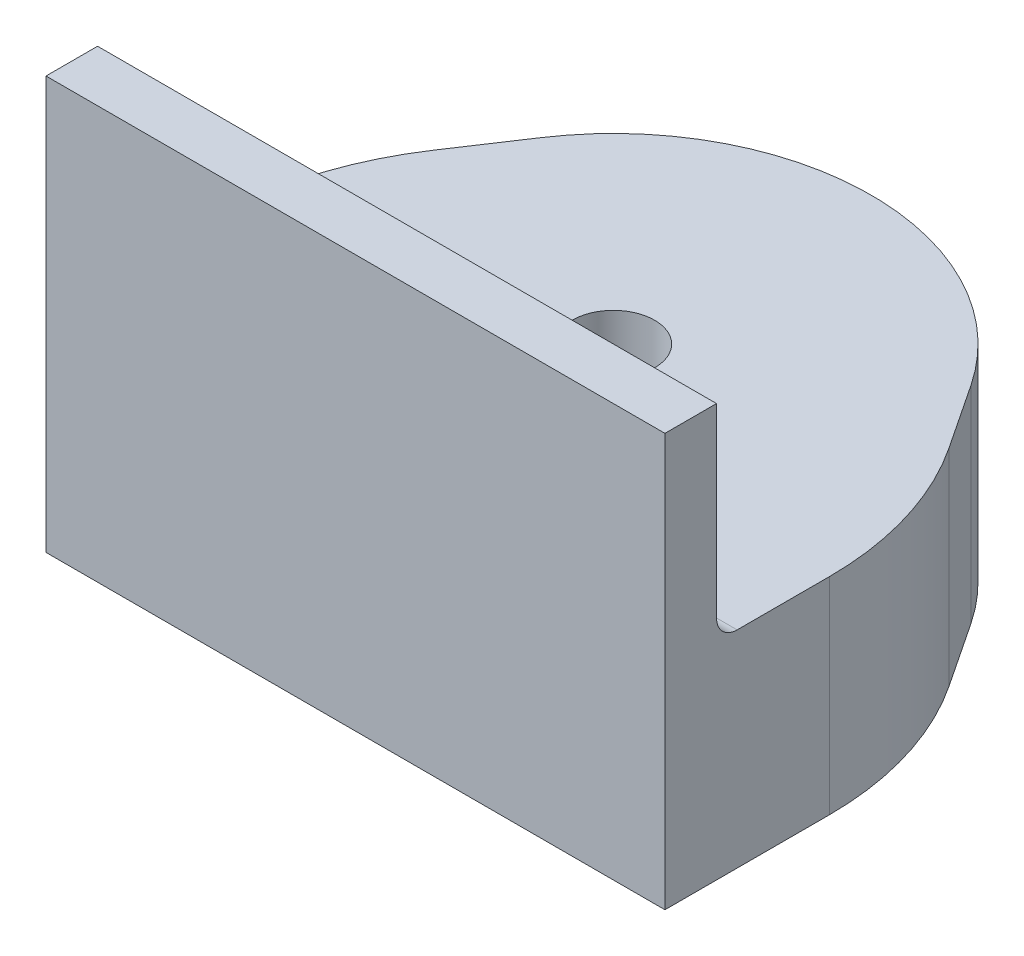
SolidWorks part; units mm, degrees
ref_plane "Front Plane" through (0, 0, 0) normal (0, 0, 1) x (1, 0, 0)
ref_plane "Top Plane" through (0, 0, 0) normal (0, 1, 0) x (1, 0, 0)
ref_plane "Right Plane" through (0, 0, 0) normal (1, 0, 0) x (0, 0, -1)
sketch "Sketch1" plane through (0, 0, 0) normal (0, 1, 0) x (1, 0, 0)
  line L0 (30, -25) -> (-30, -25)
  line L5 (-30, -25) -> (-30, 0)
  line L6 (-30, 0) -> (-20.8333, 13.8193)
  line L7 (0, 0) -> (0, -25) construction
  line L8 (30, -25) -> (30, 0)
  line L9 (30, 0) -> (20.8333, 13.8193)
  circle A0 centre (0, 0) radius 4
  arc A1 (20.8333, 13.8193) -> (-20.8333, 13.8193) centre (0, 0) ccw
  point P5 (-51.8317, 0)
  dimension "D1" = 8
  dimension "D2" = 50
  dimension "D3" = 60
extrude "Boss-Extrude1" add sketch "Sketch1" along normal blind 20
sketch "Sketch2" plane through (0, 20, 0) normal (0, 1, 0) x (1, 0, 0)
  line L0 (30, -25) -> (30, 0) construction
  line L1 (-30, -25) -> (30, -25)
  line L2 (-30, -25) -> (-30, -20)
  line L3 (-30, -20) -> (30, -20)
  line L4 (30, -25) -> (30, -20)
  dimension "D1" = 5
extrude "Boss-Extrude2" add sketch "Sketch2" along normal blind 20
fillet "Fillet2" radius 2 1 edges at (0, 20, 20)
fillet "Fillet3" radius 30 2 edges at (30, 10, 0) (-30, 10, 0)
